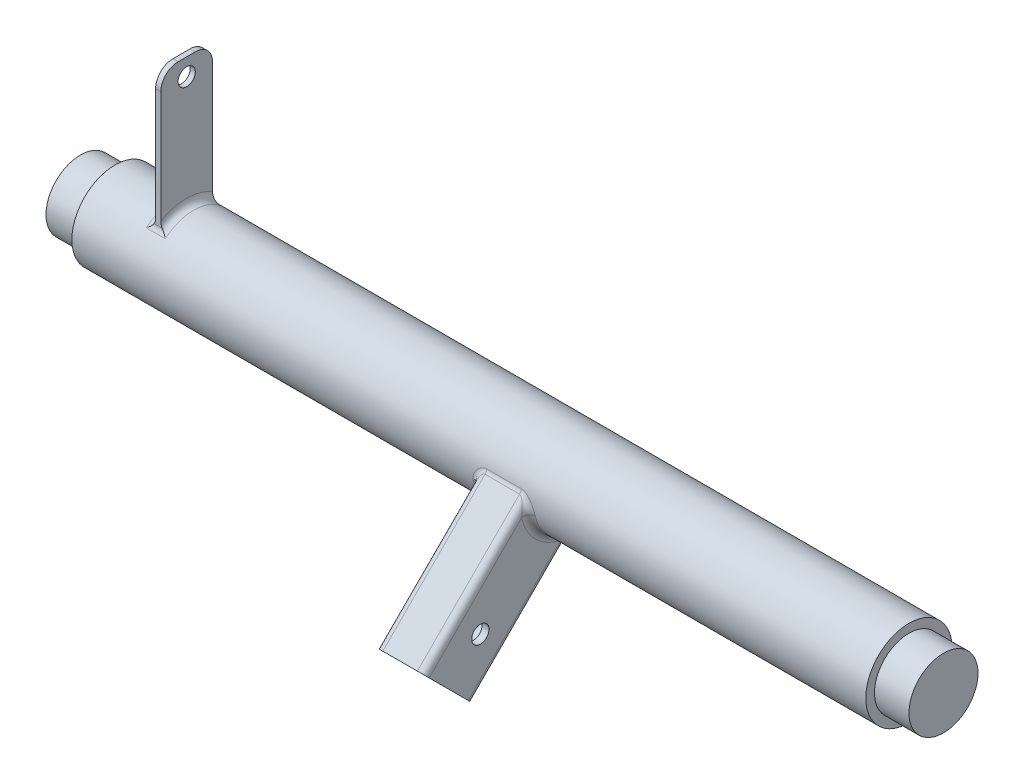
SolidWorks part; units mm, degrees
ref_plane "Front Plane" through (0, 0, 0) normal (0, 0, 1) x (1, 0, 0)
ref_plane "Top Plane" through (0, 0, 0) normal (0, 1, 0) x (1, 0, 0)
ref_plane "Right Plane" through (0, 0, 0) normal (1, 0, 0) x (0, 0, -1)
sketch "Sketch1" plane through (0, 0, 0) normal (1, 0, 0) x (0, 0, -1)
  circle A0 centre (0, 0) radius 12.5
extrude "Boss-Extrude1" add sketch "Sketch1" along normal blind 250
sketch "Sketch3" plane through (0, 0, 0) normal (-1, 0, 0) x (0, 0, 1)
  circle A0 centre (0, 0) radius 10
  circle A1 centre (0, 0) radius 12.5
  dimension "D1" = 20
extrude "Cut-Extrude1" cut sketch "Sketch3" against normal blind 10
sketch "Sketch4" plane through (250, 0, 0) normal (1, 0, 0) x (0, 0, -1)
  circle A0 centre (0, 0) radius 10
  circle A1 centre (0, 0) radius 12.5
  dimension "D1" = 25
  dimension "D2" = 20
extrude "Cut-Extrude2" cut sketch "Sketch4" against normal blind 10
sketch "Sketch5" plane through (0, 0, 0) normal (0, 1, 0) x (1, 0, 0)
  line L2 (29.25, 7.5) -> (29.25, -7.5)
  line L4 (30.75, 7.5) -> (30.75, -7.5)
  line L5 (29.55, 7.5) -> (30.45, -7.5) construction
  line L6 (29.55, -7.5) -> (30.45, 7.5) construction
  line L7 (0, 0) -> (27.1403, 0) construction
  line L8 (30.75, -7.5) -> (29.25, -7.5)
  line L9 (30.75, 7.5) -> (29.25, 7.5)
  point P0 (30, 0)
  dimension "D2" = 30
  dimension "D3" = 0
extrude "Boss-Extrude2" add sketch "Sketch5" along normal blind 50
sketch "Sketch6" plane through (29.25, 0, 0) normal (-1, 0, 0) x (0, 0, 1)
  line L0 (-7.5, 50) -> (7.5, 50) construction
  circle A0 centre (0, 45) radius 2.5
  dimension "D1" = 5
extrude "Cut-Extrude3" cut sketch "Sketch6" against normal blind 50
sketch "Sketch7" plane through (0, 0, 0) normal (-1, 0, 0) x (0, 0, 1)
  line L0 (0, 0) -> (0, 10) construction
  line L1 (0, 0) -> (7.0711, 7.0711) construction
  circle A0 centre (0, 0) radius 10 construction
  dimension "D1" = 45
ref_plane "Plane1" through (0, 0, 0) normal (0, 0.7071, -0.7071) x (0, 0.7071, 0.7071)
sketch "Sketch8" plane through (0, 0, 0) normal (0, 0.7071, -0.7071) x (0, 0.7071, 0.7071)
  line L0 (10, 0) -> (-10, 0) construction
  line L7 (10, 142) -> (-10, 142)
  line L13 (10, 142) -> (10, 128)
  line L14 (10, 128) -> (-10, 128)
  line L19 (-10, 142) -> (-10, 128)
  line L20 (10, 142) -> (-10, 128) construction
  line L21 (10, 128) -> (-10, 142) construction
  line L27 (8, 130) -> (-8, 130)
  line L28 (8, 130) -> (8, 140)
  line L29 (8, 140) -> (-8, 140)
  line L30 (-8, 130) -> (-8, 140)
  line L31 (8, 130) -> (-8, 140) construction
  line L32 (8, 140) -> (-8, 130) construction
  point P0 (0, 135)
  point P4 (0, 0)
  point P9 (0, 135)
  dimension "D1" = 135
  dimension "D2" = 20
  dimension "D3" = 14
  dimension "D4" = 2
  dimension "D5" = 2
extrude "Boss-Extrude3" add sketch "Sketch8" against normal blind 50
fillet "Fillet1" radius 5 2 edges at (30, 50, -7.5) (30, 50, 7.5)
sketch "Sketch9" plane through (128, 0, 0) normal (-1, 0, 0) x (0, 0, 1)
  line L0 (28.2843, -42.4264) -> (42.4264, -28.2843) construction
  circle A0 centre (26.163, -26.163) radius 2.5
  dimension "D1" = 13
extrude "Cut-Extrude4" cut sketch "Sketch9" against normal through all
fillet "Fillet2" radius 2 12 edges at (135, -12.3744, -1.7678) (128, -8.8388, 8.8388) (142, -8.8388, 8.8388) (30, 10, -7.5) (30.75, 12.5, 0) (30, 10, 7.5) (29.25, 12.5, 0) (135, 1.7678, 12.3744) (128, -27.4004, 13.2582) (142, -27.4004, 13.2582) (142, -13.2582, 27.4004) (128, -13.2582, 27.4004)
